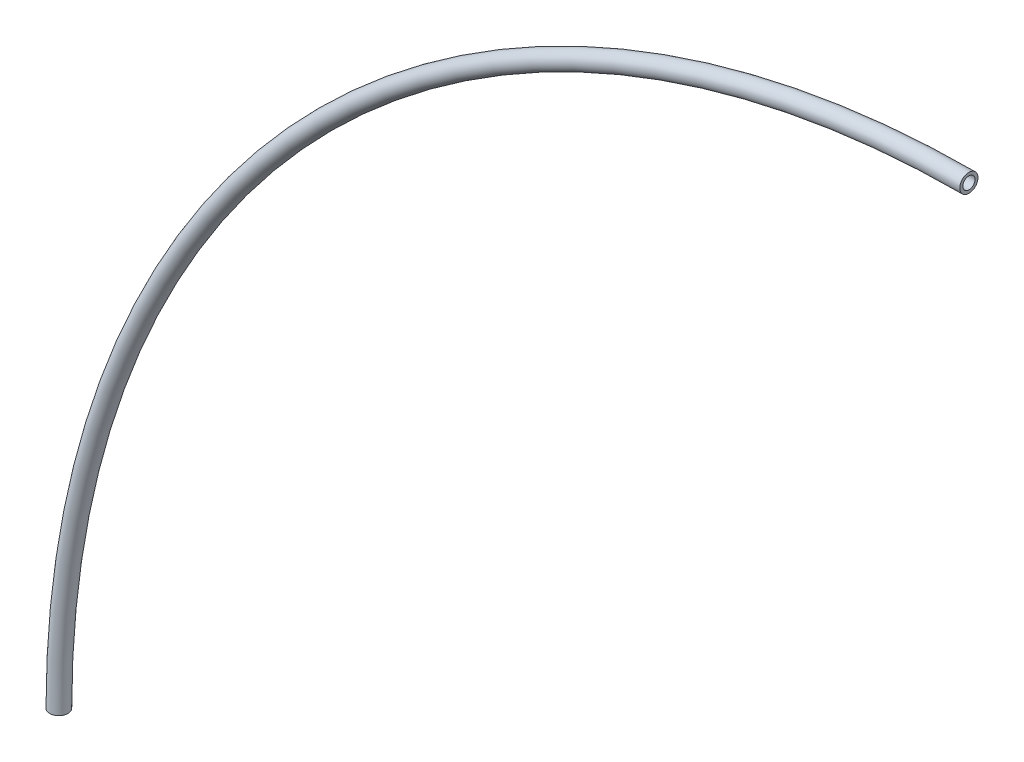
SolidWorks part; units mm, degrees
ref_plane "前视基准面" through (0, 0, 0) normal (0, 0, 1) x (1, 0, 0)
ref_plane "上视基准面" through (0, 0, 0) normal (0, 1, 0) x (1, 0, 0)
ref_plane "右视基准面" through (0, 0, 0) normal (1, 0, 0) x (0, 0, -1)
sketch "草图1" plane through (0, 0, 0) normal (0, 0, 1) x (1, 0, 0)
  circle A0 centre (0, 0) radius 600 construction
  arc A1 (-600, 0) -> (0, 600) centre (0, 0) cw
  dimension "D1" = 1200
sketch "草图2" plane through (0, 0, 0) normal (0, 1, 0) x (1, 0, 0)
  line L0 (-600, 0) -> (0, 0) construction
  line L1 (-600, 0) -> (0, 0) construction
  circle A0 centre (-600, 0) radius 6
  circle A1 centre (-600, 0) radius 4
  dimension "D1" = 12
  dimension "D2" = 8
sweep "扫描-薄件1" add path "草图1" circular profile diameter 12 parameters "D1"=2, "D3"=12
